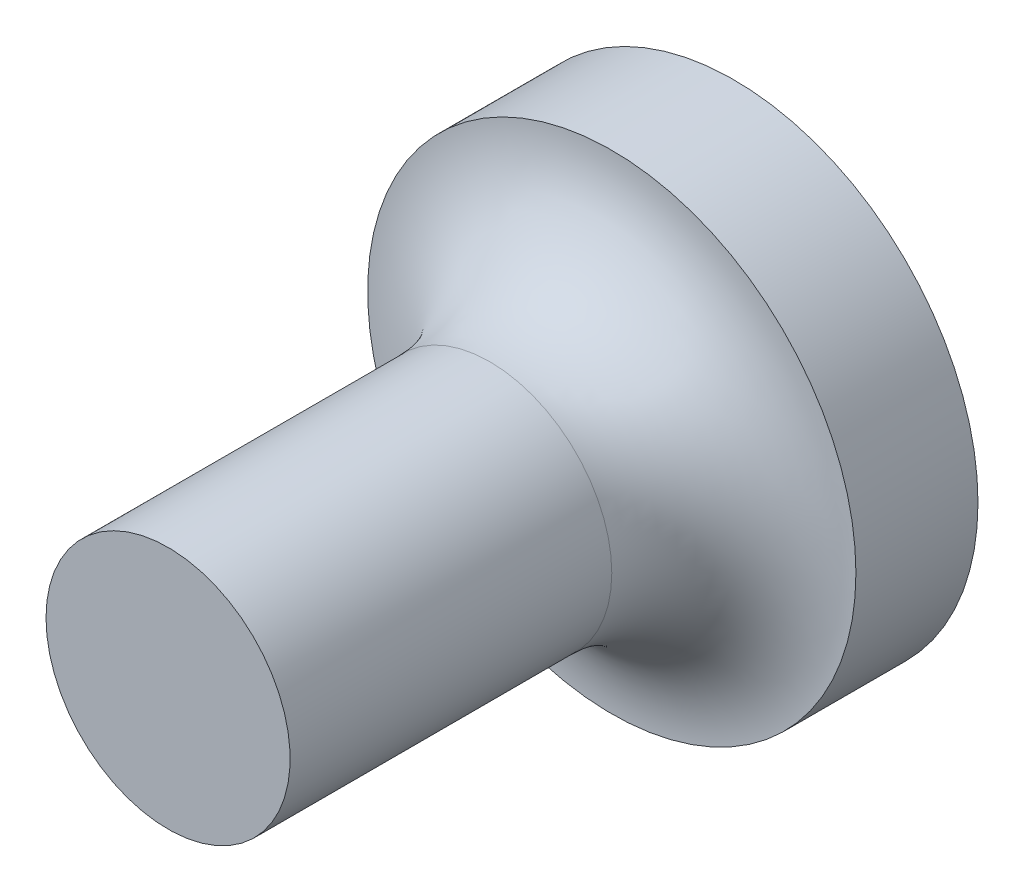
SolidWorks part; units mm, degrees
ref_plane "Plan de face" through (0, 0, 0) normal (0, 0, 1) x (1, 0, 0)
ref_plane "Plan de dessus" through (0, 0, 0) normal (0, 1, 0) x (1, 0, 0)
ref_plane "Plan de droite" through (0, 0, 0) normal (1, 0, 0) x (0, 0, -1)
sketch "Esquisse1" plane through (0, 0, 0) normal (0, 0, 1) x (1, 0, 0)
  circle A0 centre (0, 0) radius 10
  dimension "D1" = 20
extrude "Boss.-Extru.1" add sketch "Esquisse1" along normal blind 52.35
sketch "Esquisse2" plane through (0, 0, 0) normal (0, 0, 1) x (1, 0, 0)
  circle A0 centre (0, 0) radius 20
extrude "Boss.-Extru.2" add sketch "Esquisse2" along normal blind 10 from offset 6
fillet "Congé1" radius 10 1 edges at (10, 0, 16)
